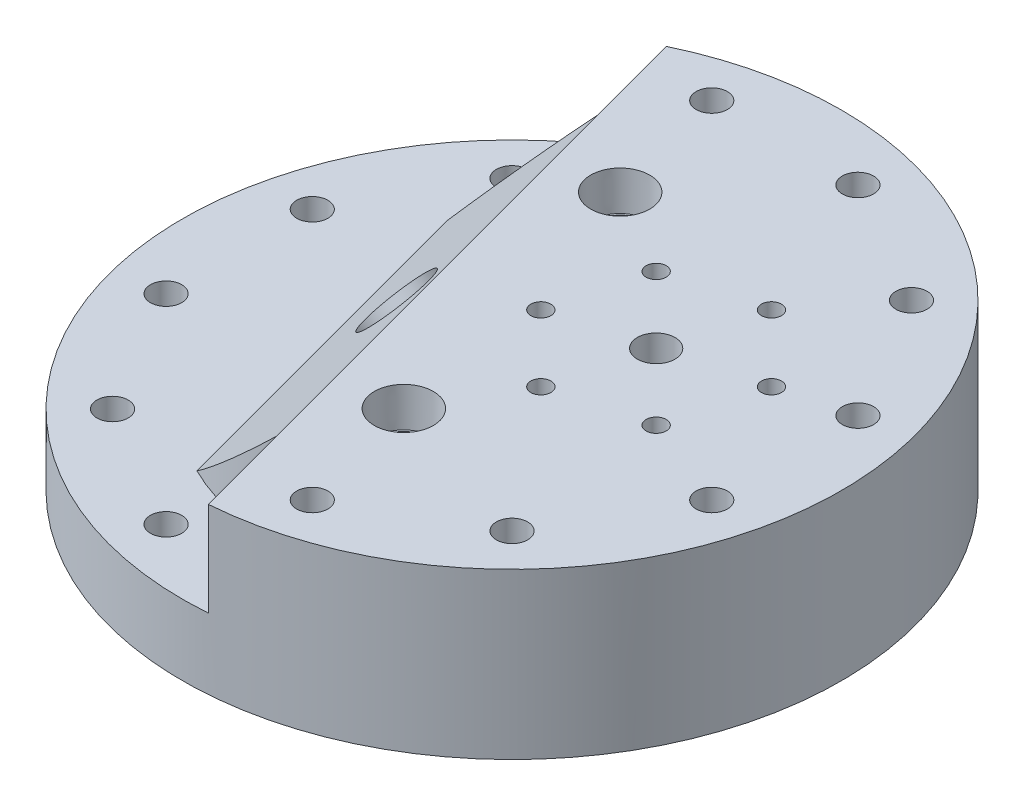
SolidWorks part; units mm, degrees
ref_plane "Front Plane" through (0, 0, 0) normal (0, 0, 1) x (1, 0, 0)
ref_plane "Top Plane" through (0, 0, 0) normal (0, 1, 0) x (1, 0, 0)
ref_plane "Right Plane" through (0, 0, 0) normal (1, 0, 0) x (0, 0, -1)
sketch "Sketch1" plane through (0, 0, 0) normal (0, 0, 1) x (1, 0, 0)
  line L0 (0, 0) -> (0, 51.199) construction
  line L1 (-54.356, 0) -> (-88.9, 0)
  line L2 (-88.9, 0) -> (-88.9, 44.45)
  line L3 (-88.9, 44.45) -> (0, 44.45)
  line L6 (0, 44.45) -> (0, 19.05)
  line L8 (-14.2875, 19.05) -> (0, 19.05)
  line L12 (-14.2875, 19.05) -> (-14.2875, 6.35)
  line L15 (-14.2875, 6.35) -> (-20.6375, 6.35)
  line L16 (-20.6375, 6.35) -> (-20.6375, 0)
  line L17 (-20.6375, 0) -> (-50.8, 0)
  line L18 (-50.8, 0) -> (-50.8, 2.54)
  line L19 (-50.8, 2.54) -> (-54.356, 2.54)
  line L20 (-54.356, 2.54) -> (-54.356, 0)
  dimension "D2" = 14.2875
  dimension "D3" = 44.45
  dimension "D4" = 50.8
  dimension "D5" = 88.9
  dimension "D6" = 12.7
  dimension "D9" = 6.35
  dimension "D12" = 20.6375
  dimension "D13" = 3.556
  dimension "D14" = 2.54
revolve "Revolve1" add sketch "Sketch1" angle 360 about L0
hole_wizard "5/16 Clearance Hole1" positions "Sketch4" profile "Sketch6" hole size "5/16" standard "ANSI Inch" end condition through all
sketch "Sketch4" plane through (0, 44.45, 0) normal (0, 1, 0) x (1, 0, 0)
  line L0 (-73.6035, -19.722) -> (0, 0) construction
  line L2 (0, 0) -> (-63.9148, 0) construction
  point P0 (-73.6035, -19.722)
  dimension "D1" = 76.2
  dimension "D2" = 15
sketch "Sketch6" plane through (-73.6035, 44.45, 19.722) normal (1, 0, 0) x (0, 0, 1)
  line L0 (0, 0) -> (0, 44.45)
  line L1 (0, 44.45) -> (4.2164, 44.45)
  line L2 (4.2164, 44.45) -> (4.2164, 0)
  line L5 (4.2164, 0) -> (0, 0)
  line L11 (0, -6.35) -> (0, 107.95) construction
  dimension "Thru Hole Dia." = 8.4328
  dimension "Thru Hole Depth" = 44.45
pattern_circular "CirPattern1" count 12 over 360 about axis through (0, 0, 0) along (0, -1, 0) of "5/16 Clearance Hole1" reverse direction yes
hole_wizard "3/8 NPT Tapped Hole1" positions "Sketch17" profile "Sketch19" size "3/8" standard "ANSI Inch" end condition through all
sketch "Sketch17" plane through (0, 44.45, 0) normal (0, 1, 0) x (1, 0, 0)
  line L0 (0, 0) -> (-55.2485, 0) construction
  line L2 (0, 0) -> (10.6828, -39.8686) construction
  point P0 (10.6828, -39.8686)
  dimension "D1" = 41.275
  dimension "D2" = 105
cosmetic thread "Hole Thread5" parameters "D1"=10.414, "D2"=17.1495
sketch "Sketch19" plane through (10.6828, 44.45, 39.8686) normal (1, 0, 0) x (0, 0, 1)
  line L0 (0, 0) -> (0, 44.45)
  line L1 (0, 44.45) -> (7.1374, 44.45)
  line L2 (-7.6537, 10.414) -> (-7.9655, 0) construction
  line L3 (7.1374, 44.45) -> (7.1374, 10.414)
  line L4 (7.1374, 10.414) -> (7.6537, 10.414)
  line L5 (7.6537, 10.414) -> (7.9655, 0)
  line L7 (7.9655, 0) -> (0, 0)
  line L8 (0, -6.35) -> (0, 107.95) construction
  line L11 (-7.1374, 10.414) -> (-7.6537, 10.414) construction
  dimension "Thru Tap Drill Dia." = 14.2748
  dimension "Thru Tap Drill Depth" = 44.45
  dimension "Thread Dia." = 15.9311
  dimension "Thread Angle" = 3.43
  dimension "Thread Depth" = 10.414
ref_axis "Axis2" through (-73.6035, 0, 19.722) along (0, 1, 0)
ref_axis "Axis3" through (73.6035, 0, -19.722) along (0, 1, 0)
ref_plane "Plane3" through (0, 0, 0) normal (-0.2588, 0, -0.9659) x (-0.9659, 0, 0.2588)
mirror "Mirror1" about plane through (0, 0, 0) normal (-0.2588, 0, -0.9659) of "3/8 NPT Tapped Hole1"
cosmetic thread "Hole Thread7" parameters "D1"=10.414, "D2"=17.1495
hole_wizard "1/2 (0.4) Diameter Hole1" positions "Sketch26" profile "Sketch28" hole size "1/2" standard "ANSI Inch" end condition through all
sketch "Sketch26" plane through (0, 44.45, 0) normal (0, 1, 0) x (1, 0, 0)
  line L0 (0, 0) -> (30.6681, 8.2175) construction
  line L1 (0, 0) -> (39.3022, 0) construction
  point P0 (30.6681, 8.2175)
  dimension "D1" = 31.75
  dimension "D2" = 15
sketch "Sketch28" plane through (30.6681, 44.45, -8.2175) normal (1, 0, 0) x (0, 0, 1)
  line L0 (0, 0) -> (0, 44.45)
  line L1 (0, 44.45) -> (5.08, 44.45)
  line L2 (5.08, 44.45) -> (5.08, 0)
  line L5 (5.08, 0) -> (0, 0)
  line L11 (0, -6.35) -> (0, 107.95) construction
  dimension "Thru Hole Dia." = 10.16
  dimension "Thru Hole Depth" = 44.45
ref_plane "Plane1" through (0, 95.25, 0) normal (0, 1, 0) x (1, 0, 0)
ref_axis "Axis1" through (30.6681, 0, -8.2175) along (0, 1, 0)
hole_wizard "Tap Drill for 1/4-28 Tap1" positions "Sketch29" profile "Sketch30" hole size "1/4-28" standard "ANSI Inch"
sketch "Sketch29" plane through (0, 44.45, 0) normal (0, 1, 0) x (1, 0, 0)
  line L0 (30.6681, 8.2175) -> (55.2027, 14.7915) construction
  line L1 (30.6681, 8.2175) -> (59.7964, 8.2175) construction
  point P0 (55.2027, 14.7915)
  dimension "D1" = 25.4
  dimension "D2" = 15
sketch "Sketch30" plane through (55.2027, 44.45, -14.7915) normal (1, 0, 0) x (0, 0, 1)
  line L0 (0, 0) -> (0, 17.5004)
  line L1 (0, 17.5004) -> (2.7051, 15.875)
  line L2 (2.7051, 15.875) -> (2.7051, 0)
  line L5 (2.7051, 0) -> (0, 0)
  line L10 (0, 17.5004) -> (-2.7051, 15.875) construction
  line L11 (0, -6.35) -> (0, 107.95) construction
  dimension "Hole Dia." = 5.4102
  dimension "Hole Depth" = 15.875
  dimension "Drill Angle" = 118
pattern_circular "CirPattern2" count 6 over 360 about axis through (30.6681, 0, -8.2175) along (0, 1, 0) of "Tap Drill for 1/4-28 Tap1"
sketch "Sketch31" plane through (0, 44.45, 0) normal (0, 1, 0) x (1, 0, 0)
  line L1 (0, -63.5) -> (6.7374, -88.6443)
  line L2 (0, -63.5) -> (0, 0) construction
  line L3 (0, 0) -> (-31.75, 54.9926) construction
  line L4 (73.6035, 19.722) -> (0, 0) construction
  line L5 (0, 0) -> (-73.6035, -19.722) construction
  line L6 (-31.75, 54.9926) -> (-38.4874, 80.1369)
  arc A0 (-38.4874, 80.1369) -> (6.7374, -88.6443) centre (0, 0) ccw
  circle A1 centre (0, 0) radius 88.9 construction
  arc A2 (-31.75, 54.9926) -> (0, -63.5) centre (0, 0) ccw
  point P8 (6.7374, -88.6443)
  point P13 (0, 0)
  point P14 (6.7374, -88.6443)
  dimension "D1" = 75
  dimension "D2" = 75
  dimension "D3" = 25.4
extrude "Cut-Extrude1" cut sketch "Sketch31" against normal blind 25.4
ref_plane "Plane2" through (0.7001, 0, 2.6129) normal (-0.2588, 0, -0.9659) x (-0.9659, 0, 0.2588)
sketch "Sketch33" plane through (0.7001, 0, 2.6129) normal (-0.2588, 0, -0.9659) x (-0.9659, 0, 0.2588)
  line L0 (16.435, 44.45) -> (41.835, 19.05)
  line L1 (88.9, 19.05) -> (16.435, 19.05) construction
  line L2 (41.835, 19.05) -> (63.5, 19.05)
  line L3 (63.5, 19.05) -> (63.5, 44.45)
  line L4 (63.5, 44.45) -> (16.435, 44.45)
  point P5 (44.9515, 19.05)
  dimension "D1" = 45
extrude "Cut-Extrude2" cut sketch "Sketch33" against normal through all and the other way through all
hole_wizard "1/2 NPT Tapped Hole1" positions "Sketch34" profile "Sketch35" size "1/2" standard "ANSI Inch"
sketch "Sketch34" plane through (-29.4052, 30.4425, 7.8791) normal (-0.683, 0.7071, 0.183) x (0.7304, 0.6612, 0.1711)
  line L0 (0, 0) -> (18.5242, 7.0195) construction
  line L1 (40.2587, -50.3369) -> (-3.2103, 64.3759) construction
  point P0 (6.6483, 2.5193)
  point P11 (7.8623, -1.3006)
  point P12 (3.4386, 1.303)
  dimension "D1" = 12.7
sketch "Sketch35" plane through (-24.5493, 35.4697, 6.578) normal (0.6325, 0.4472, 0.6325) x (-0.3654, -0.5477, 0.7527)
  line L0 (0, 0) -> (0, 40.2895)
  line L1 (8.9281, 34.925) -> (0, 40.2895)
  line L2 (-8.9281, 34.925) -> (0, 40.2895) construction
  line L3 (8.9281, 34.925) -> (8.9281, 13.462)
  line L4 (8.9281, 13.462) -> (9.4797, 13.462)
  line L5 (9.4797, 13.462) -> (9.8828, 0)
  line L6 (-9.4797, 13.462) -> (-9.8828, 0) construction
  line L7 (9.8828, 0) -> (0, 0)
  line L8 (0, -6.35) -> (0, 107.95) construction
  line L11 (-8.9281, 13.462) -> (-9.4797, 13.462) construction
  dimension "Tap Drill Dia." = 17.8562
  dimension "Tap Drill Depth" = 34.925
  dimension "Thread Dia." = 19.7656
  dimension "Thread Angle" = 3.43
  dimension "Thread Depth" = 13.462
  dimension "Drill Angle" = 118
cosmetic thread "Hole Thread6" parameters "D1"=13.462, "D2"=21.3288
sketch "Sketch36" plane through (0, 0, 0) normal (0, -1, 0) x (1, 0, 0)
  circle A0 centre (30.6681, -8.2175) radius 6.6675
  circle A1 centre (30.6681, -8.2175) radius 9.7155
  circle A2 centre (30.6681, -8.2175) radius 5.08 construction
  dimension "D1" = 3.048
  dimension "D2" = 1.5875
extrude "Cut-Extrude3" cut sketch "Sketch36" against normal blind 2.54
equation "\"D2@Sketch31\"=\"D1@Sketch31\""
